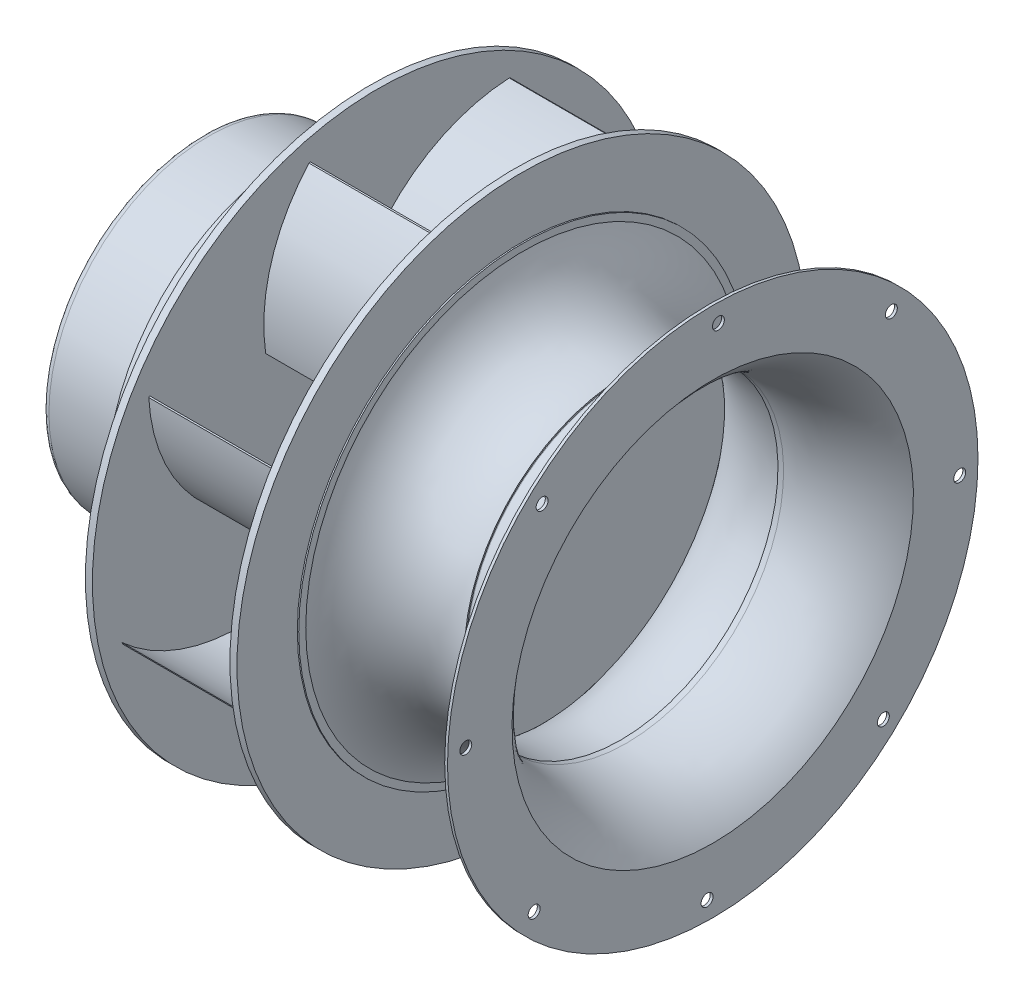
SolidWorks part; units mm, degrees
ref_plane "Front Plane" through (0, 0, 0) normal (0, 0, 1) x (1, 0, 0)
ref_plane "Top Plane" through (0, 0, 0) normal (0, 1, 0) x (1, 0, 0)
ref_plane "Right Plane" through (0, 0, 0) normal (1, 0, 0) x (0, 0, -1)
sketch "Sketch1" plane through (0, 0, 0) normal (0, 0, 1) x (1, 0, 0)
  line L0 (0, 0) -> (831.9083, 0) construction
  line L1 (0, 0) -> (0, 109)
  line L2 (5, 114) -> (70, 114)
  line L3 (70, 114) -> (70, 138)
  line L4 (70, 138) -> (83.9, 138)
  line L5 (83.9, 138) -> (83.9, 98)
  line L6 (83.9, 98) -> (88.9, 98)
  line L7 (88.9, 98) -> (88.9, 133)
  line L8 (88.9, 133) -> (98.9, 133)
  line L9 (98.9, 133) -> (98.9, 98)
  line L10 (98.9, 98) -> (120, 98)
  line L11 (120, 98) -> (120, 0)
  line L12 (120, 0) -> (0, 0)
  arc A0 (5, 114) -> (0, 109) centre (5, 109) ccw
  point P16 (0, 114)
  dimension "D10" = 5
  dimension "D1" = 114
  dimension "D2" = 24
  dimension "D3" = 70
  dimension "D4" = 40
  dimension "D5" = 35
  dimension "D6" = 5
  dimension "D7" = 13.9
  dimension "D8" = 10
  dimension "D9" = 50
revolve "Revolve1" add sketch "Sketch1" angle 360 about L0
sketch "Sketch2" plane through (120, 0, 0) normal (1, 0, 0) x (0, 0, -1)
  circle A0 centre (0, 0) radius 203
  dimension "D1" = 406
extrude "Extrude1" add sketch "Sketch2" along normal blind 5
sketch "Sketch9" plane through (120, 0, 0) normal (-1, 0, 0) x (0, 0, 1)
  circle A0 centre (0, 0) radius 198
  circle A1 centre (0, 0) radius 70
  circle A2 centre (0, 0) radius 203 construction
  dimension "D1" = 5
  dimension "D2" = 140
extrude "Extrude7" cut sketch "Sketch9" against normal blind 3
ref_plane "Plane1" through (223, 0, 0) normal (1, 0, 0) x (0, 0, -1)
sketch "Sketch3" plane through (223, 0, 0) normal (1, 0, 0) x (0, 0, -1)
  circle A0 centre (0, 0) radius 203
  dimension "D1" = 406
extrude "Extrude2" add sketch "Sketch3" along normal blind 5 separate body
sketch "Sketch4" plane through (125, 0, 0) normal (1, 0, 0) x (0, 0, -1)
  line L0 (0, 0) -> (0, 188) construction
  line L1 (0, 0) -> (101.5, 175.8032) construction
  line L2 (0, 112.5) -> (0.866, 112)
  line L3 (94, 162.8128) -> (94.866, 162.3128)
  circle A0 centre (0, 0) radius 188 construction
  circle A1 centre (0, 0) radius 203 construction
  circle A2 centre (0, 0) radius 112.5 construction
  arc A3 (0, 112.5) -> (94, 162.8128) centre (100.354, 37.9744) cw
  arc A4 (0.866, 112) -> (94.866, 162.3128) centre (101.2201, 37.4744) cw
  dimension "D1" = 15
  dimension "D2" = 225
  dimension "D6" = 125
  dimension "D7" = 125
  dimension "D3" = 30
  dimension "D4" = 60
  dimension "D5" = 1
extrude "Extrude3" add sketch "Sketch4" along normal up to surface (103 mm away) up to face at (228, 0, -203)
ref_axis "Axis1" through (253.5503, 0, 0) along (-1, 0, 0)
pattern_circular "CirPattern1" count 8 over 360 about axis through (253.5503, 0, 0) along (-1, 0, 0) of "Extrude3"
sketch "Sketch5" plane through (0, 0, 0) normal (0, 0, 1) x (1, 0, 0)
  line L0 (0, 0) -> (527.2916, 0) construction
  line L1 (253.5503, 0) -> (75.411, 0) construction
  line L2 (228, 160) -> (229, 160)
  line L3 (229, 160) -> (229, 155)
  line L4 (228, 160) -> (228, 155)
  line L5 (302, 115) -> (302, 114)
  line L6 (70, 138) -> (70, -138) construction
  line L7 (228, -203) -> (228, 203) construction
  arc A0 (229, 155) -> (302, 115) centre (286.2675, 172.9007) ccw
  arc A1 (228, 155) -> (302, 114) centre (285.6228, 171.7216) ccw
  dimension "D7" = 60
  dimension "D8" = 60
  dimension "D1" = 114
  dimension "D2" = 1
  dimension "D3" = 1
  dimension "D4" = 5
  dimension "D5" = 160
  dimension "D6" = 232
revolve "Revolve2" add sketch "Sketch5" angle 360 about L0
ref_plane "Plane3" through (364, 0, 0) normal (1, 0, 0) x (0, 0, -1)
sketch "Sketch6" plane through (0, 0, 0) normal (0, 0, 1) x (1, 0, 0)
  line L0 (364, 189) -> (362, 189)
  line L1 (364, -251.35) -> (364, 251.35) construction
  line L2 (362, 189) -> (362, 143)
  line L3 (0, 0) -> (615.1417, 0) construction
  line L4 (0, 114) -> (0, -114) construction
  line L5 (253.5503, 0) -> (75.411, 0) construction
  line L6 (364, 189) -> (364, 143)
  line L7 (298.5, 114) -> (302.5, 114)
  line L8 (298.5, 114) -> (298.5, 112)
  line L9 (298.5, 112) -> (302.5, 112)
  arc A0 (302.5, 114) -> (362, 143) centre (300.3398, 193.9708) ccw
  arc A1 (302.5, 112) -> (364, 143) centre (300.7475, 191.9808) ccw
  dimension "D7" = 80
  dimension "D8" = 80
  dimension "D1" = 189
  dimension "D2" = 2
  dimension "D3" = 143
  dimension "D4" = 65.5
  dimension "D5" = 114
  dimension "D6" = 4
revolve "Revolve3" add sketch "Sketch6" angle 360 about L3
sketch "Sketch7" plane through (364, 0, 0) normal (1, 0, 0) x (0, 0, -1)
  line L0 (0, 0) -> (0, 176) construction
  line L1 (0, 0) -> (-160.5981, 168.1205) construction
  circle A0 centre (0, 0) radius 176 construction
  circle A1 centre (-121.571, 127.2654) radius 4.25
  circle A2 centre (4.0265, 175.9539) radius 4.25
  circle A3 centre (127.2654, 121.571) radius 4.25
  circle A4 centre (175.9539, -4.0265) radius 4.25
  circle A5 centre (121.571, -127.2654) radius 4.25
  circle A6 centre (-4.0265, -175.9539) radius 4.25
  circle A7 centre (-127.2654, -121.571) radius 4.25
  circle A8 centre (-175.9539, 4.0265) radius 4.25
  point P24 (0, 0)
  dimension "D1" = 352
  dimension "D2" = 8.5
  dimension "D3" = 8
extrude "Extrude5" cut sketch "Sketch7" against normal blind 5
sketch "Sketch8" plane through (0, 0, 0) normal (1, 0, 0) x (0, 0, -1)
  line L0 (0, 0) -> (0, 126) construction
  circle A0 centre (0, 0) radius 126 construction
  circle A1 centre (0, 126) radius 5
  dimension "D1" = 252
  dimension "D2" = 10
extrude "Extrude6" cut sketch "Sketch8" along normal up to surface (83.9 mm away) up to face at (83.9, 0, 138)
pattern_circular "CirPattern3" count 4 over 360 about axis through (253.5503, 0, 0) along (-1, 0, 0) of "Extrude6"
